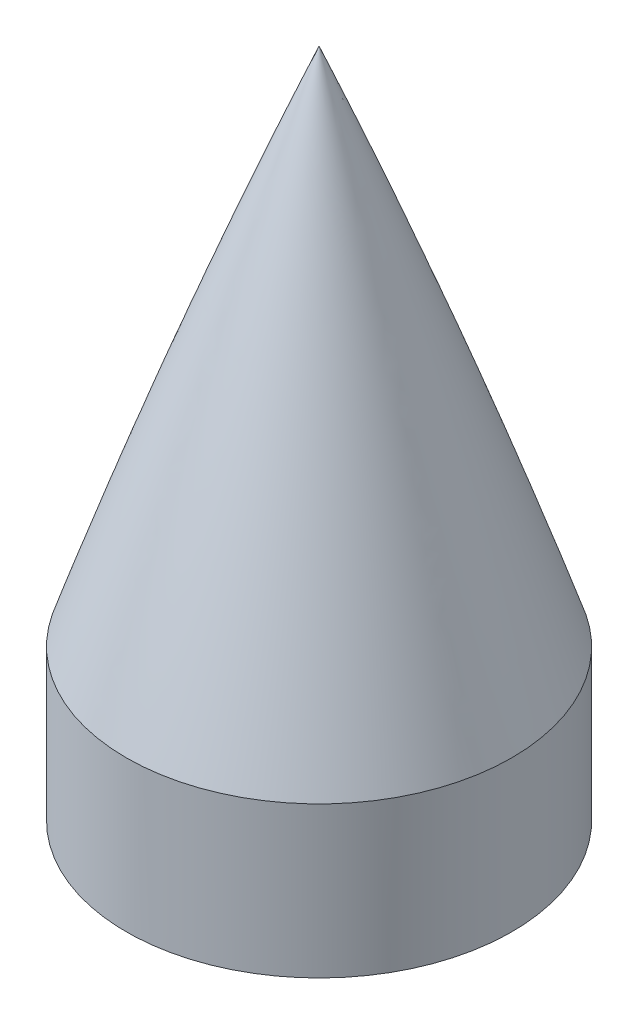
SolidWorks part; units mm, degrees
other "Markup1"
sketch "Sketch4" plane through (78.16, -154.2442, 78.16) normal (0.9651, -0.1718, 0.1975) x (-0.1686, -0.9851, -0.0334)
material "PE High Density Film"
ref_plane "Front Plane" through (0, 0, 0) normal (0, 0, 1) x (1, 0, 0)
ref_plane "Top Plane" through (0, 0, 0) normal (0, 1, 0) x (1, 0, 0)
ref_plane "Right Plane" through (0, 0, 0) normal (1, 0, 0) x (0, 0, -1)
sketch "Sketch1" plane through (0, 0, 0) normal (0, 0, 1) x (1, 0, 0)
  line L3 (0, 0) -> (0, 398.8705) construction
  line L6 (0, 400) -> (0, 402.7567)
  line L9 (0, 400) -> (0, 396.4892)
  line L10 (78.35, 0) -> (-964.0394, 0) construction
  line L11 (0, 411.0234) -> (0, 614.1078) construction
  line L14 (78.35, 0) -> (78.35, -150)
  line L15 (78.35, -150) -> (80.75, -150)
  line L16 (80.75, 0) -> (80.75, -150)
  arc A0 (78.35, 0) -> (0, 396.4892) centre (-964.0394, 0) ccw
  arc A1 (80.75, 0) -> (0, 402.7567) centre (-964.0394, 0) ccw
  circle A2 centre (-964.0394, 0) radius 1042.3894 construction
  circle A3 centre (-964.0394, 0) radius 1044.7894 construction
  point P11 (0, 400)
  dimension "D5" = 1042.3894
  dimension "D1" = 400
  dimension "D2" = 3.5108
  dimension "D3" = 2.4
  dimension "D4" = 78.35
  dimension "D6" = 150
  dimension "D7" = 2.4
revolve "Revolve3" add sketch "Sketch1" angle 360 about L6 reverse direction yes
sketch "Sketch5" plane through (0, -150, 0) normal (0, -1, 0) x (1, 0, 0)
  circle A0 centre (0, 0) radius 78.35
extrude "Boss-Extrude1" add sketch "Sketch5" against normal up to surface (150 mm away) separate body
delete or keep bodies "Body-Delete/Keep 1" type delete bodies bodies 101
ref_plane "Plane2" through (0, 396.4892, 0) normal (0, 1, 0) x (1, 0, 0)
ref_plane "Plane3" through (0, 327.4892, 0) normal (0, 1, 0) x (1, 0, 0)
split "Split1" trim tools "Plane3" bodies to split 109 resulting bodies 110 111
delete or keep bodies "Body-Delete/Keep 2" type delete bodies bodies 111
shell "Shell1" thickness 3 removed face at (0, 327.4892, 25.5699)
sketch "Sketch6" plane through (0, 327.4892, 0) normal (0, -1, 0) x (1, 0, 0)
  circle A0 centre (0, 0) radius 25.5699 construction
  circle A1 centre (0, 0) radius 22.4094 construction
  circle A2 centre (0, 0) radius 25.5699
  circle A3 centre (0, 0) radius 22.4094
extrude "Boss-Extrude2" add sketch "Sketch6" along normal blind 20
